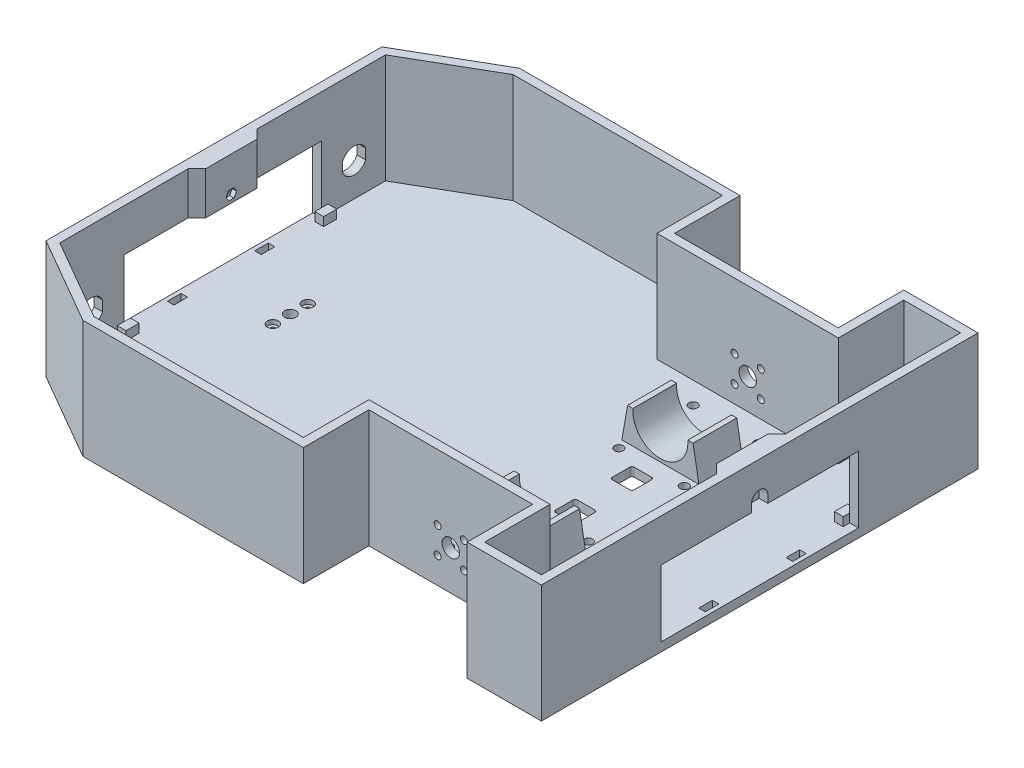
SolidWorks part; units mm, degrees
ref_plane "Front Plane" through (0, 0, 0) normal (0, 0, 1) x (1, 0, 0)
ref_plane "Top Plane" through (0, 0, 0) normal (0, 1, 0) x (1, 0, 0)
ref_plane "Right Plane" through (0, 0, 0) normal (1, 0, 0) x (0, 0, -1)
sketch "Sketch1" plane through (0, 0, 0) normal (0, 1, 0) x (1, 0, 0)
  line L0 (-85, 100) -> (125, 100)
  line L1 (-125, 100) -> (125, 100) construction
  line L2 (-125, 100) -> (-125, -100) construction
  line L3 (-125, -100) -> (125, -100) construction
  line L4 (125, 100) -> (125, -100) construction
  line L6 (125, 100) -> (125, -100)
  line L8 (-125, -76.906) -> (-125, 76.906)
  line L9 (-125, 76.906) -> (-85, 100)
  line L10 (-125, 0) -> (125, 0) construction
  line L12 (-85, -100) -> (125, -100)
  line L13 (-125, -76.906) -> (-85, -100)
  point P4 (0, 100)
  point P6 (-125, 0)
  point P9 (0, 0)
  dimension "D1" = 250
  dimension "D2" = 200
  dimension "D3" = 60
  dimension "D5" = 40
extrude "Boss-Extrude1" add sketch "Sketch1" along normal blind 54
shell "Shell1" thickness 4 removed face at (-28.3333, 54, 0)
sketch "Sketch7" plane through (0, 54, 0) normal (0, 1, 0) x (1, 0, 0)
  line L0 (-85, -100) -> (125, -100) construction
  line L1 (16, -70) -> (91, -70)
  line L2 (16, -70) -> (16, -100)
  line L3 (16, -100) -> (91, -100)
  line L4 (91, -70) -> (91, -100)
  line L5 (121, -96) -> (121, 96) construction
  dimension "D1" = 30
  dimension "D2" = 75
  dimension "D3" = 30
extrude "Cut-Extrude4" cut sketch "Sketch7" against normal up to next
sketch "Sketch8" plane through (0, 4, 0) normal (0, 1, 0) x (1, 0, 0)
  line L0 (16, -96) -> (16, -70)
  line L1 (16, -70) -> (91, -70)
  line L2 (91, -70) -> (91, -96)
  line L3 (12, -96) -> (12, -66)
  line L4 (12, -66) -> (95, -66)
  line L5 (95, -66) -> (95, -96)
  line L6 (16, -96) -> (12, -96)
  line L7 (91, -96) -> (95, -96)
  dimension "D1" = 4
extrude "Boss-Extrude3" add sketch "Sketch8" along normal up to surface (50 mm away) contours L3 L4 L5 L7 L2 L1 L0 L6 up to face at (-7.741, 54, 24.5)
sketch "Sketch9" plane through (0, 0, 70) normal (0, 0, 1) x (1, 0, 0)
  line L1 (91, 54) -> (16, 54) construction
  line L2 (91, 0) -> (16, 0) construction
  point P4 (53.5, 54)
  line B0 (59.5104, 11.9896) -> (47.4896, 24.0104) construction
  circle B1 centre (53.5, 18) radius 4
  circle B2 centre (59.5104, 11.9896) radius 1.6
  circle B3 centre (47.4896, 24.0104) radius 1.6
  circle B4 centre (53.5, 18) radius 12.5 construction
  line B5 (47.4896, 11.9896) -> (59.5104, 24.0104) construction
  circle B6 centre (53.5, 18) radius 4
  circle B7 centre (47.4896, 11.9896) radius 1.6
  circle B8 centre (59.5104, 24.0104) radius 1.6
  circle B9 centre (53.5, 18) radius 12.5 construction
  dimension "D1" = 18
sketch_block_instance "Block-JGA25-371-1"
sketch_block "Block1" parameters "D1"=8, "D3"=3.2, "D4"=25, "D2"=17
sketch_block_instance "Block1-1"
extrude "Cut-Extrude5" cut sketch "Sketch9" against normal up to surface (4 mm away) contours B1 | B7 | B3 | B8 | B2 region at (53.5, 18, 70) region at (59.5104, 11.9896, 70) region at (47.4896, 24.0104, 70) region at (47.4896, 11.9896, 70) region at (59.5104, 24.0104, 70) up to face at (53.5, 29, 66)
sketch "Sketch10" plane through (0, 4, 0) normal (0, 1, 0) x (1, 0, 0)
  line L0 (95, -66) -> (12, -66) construction
  line L1 (38.5, -26) -> (68.5, -26)
  line L2 (38.5, -26) -> (38.5, -46)
  line L3 (38.5, -46) -> (68.5, -46)
  line L4 (68.5, -26) -> (68.5, -46)
  line L5 (91, -70) -> (16, -70) construction
  point P9 (53.5, -70)
  point P10 (53.5, -46)
  dimension "D1" = 30
  dimension "D2" = 20
  dimension "D3" = 20
extrude "Boss-Extrude4" add sketch "Sketch10" along normal blind 15
sketch "Sketch11" plane through (0, 0, 46) normal (0, 0, 1) x (1, 0, 0)
  circle A0 centre (53.5, 18) radius 12.6
  dimension "D1" = 25.2
extrude "Cut-Extrude6" cut sketch "Sketch11" against normal up to surface (20 mm away) up to face at (53.5, 11.5, 26)
sketch "Sketch12" plane through (0, 4, 0) normal (0, 1, 0) x (1, 0, 0)
  line L0 (12, -66) -> (95, -66) construction
  line L1 (48.5, -8) -> (58.5, -8)
  line L2 (48.5, -8) -> (48.5, -18)
  line L3 (48.5, -18) -> (58.5, -18)
  line L4 (58.5, -8) -> (58.5, -18)
  line L5 (91, -70) -> (16, -70) construction
  point P9 (53.5, -70)
  point P10 (53.5, -18)
  dimension "D1" = 10
  dimension "D2" = 48
extrude "Cut-Extrude7" cut sketch "Sketch12" against normal through all
fillet "Fillet1" radius 1 4 edges at (48.5, 2, 18) (58.5, 2, 18) (58.5, 2, 8) (48.5, 2, 8)
chamfer "Chamfer1" distance 15 angle 10 2 edges at (38.5, 4, 36) (68.5, 4, 36) first distance on face at (38.5, 11.5, 36) first distance on face at (68.5, 11.5, 36)
sketch "Sketch36" plane through (0, 4, 0) normal (0, 1, 0) x (1, 0, 0)
  line L0 (91, -70) -> (16, -70) construction
  line L2 (38.5, -22) -> (68.5, -22) construction
  line L3 (38.5, -22) -> (38.5, -56) construction
  line L4 (38.5, -56) -> (68.5, -56) construction
  line L5 (68.5, -22) -> (68.5, -56) construction
  circle A0 centre (68.5, -56) radius 2
  circle A1 centre (38.5, -56) radius 2
  circle A2 centre (38.5, -22) radius 2
  circle A3 centre (68.5, -22) radius 2
  point P6 (53.5, -70)
  point P12 (53.5, -56)
  dimension "D1" = 4
  dimension "D2" = 30
  dimension "D3" = 34
extrude "Cut-Extrude22" cut sketch "Sketch36" against normal up to next
mirror "Mirror2" about plane through (0, 0, 0) normal (0, 0, 1) of "Cut-Extrude22", "Fillet1", "Cut-Extrude7", "Cut-Extrude5", "Boss-Extrude3", "Cut-Extrude4", "Cut-Extrude6", "Boss-Extrude4", "Chamfer1"
sketch "Sketch13" plane through (0, 4, 0) normal (0, 1, 0) x (1, 0, 0)
  line L0 (-90, 0) -> (90, 0) construction
  circle A0 centre (-90, 0) radius 2.6
  circle A1 centre (90, 0) radius 2.6
  point P2 (0, 0)
  circle B0 centre (-90.0005, -8) radius 1.1
  circle B1 centre (-89.9995, 8) radius 1.1
  circle B2 centre (89.9995, -8) radius 1.1
  circle B3 centre (90.0005, 8) radius 1.1
  dimension "D2" = 5.2
  dimension "D1" = 180
sketch_block_instance "Ball-Caster-1"
sketch_block "Ball-Caster" parameters "D1"=16, "D2"=2.2, "D3"=16
sketch_block_instance "Ball-Caster-2"
extrude "Cut-Extrude8" cut sketch "Sketch13" against normal blind 10
sketch "Sketch14" plane through (0, 4, 0) normal (0, 1, 0) x (1, 0, 0)
  circle A0 centre (-89.9995, 8) radius 2.5
  circle A1 centre (-90.0005, -8) radius 2.5
  circle A2 centre (90.0005, 8) radius 2.5
  circle A3 centre (89.9995, -8) radius 2.5
  dimension "D1" = 5
extrude "Cut-Extrude9" cut sketch "Sketch14" against normal blind 2
sketch "Sketch16" plane through (-125, 0, 0) normal (-1, 0, 0) x (0, 0, 1)
  line L1 (-45.25, 34.5) -> (45.25, 34.5)
  line L2 (-45.25, 34.5) -> (-45.25, 4)
  line L3 (-45.25, 4) -> (45.25, 4)
  line L4 (45.25, 34.5) -> (45.25, 4)
  line L5 (-76.906, 0) -> (76.906, 0) construction
  point P6 (0, 34.5)
  dimension "D1" = 30.5
  dimension "D2" = 90.5
  dimension "D5" = 4
extrude "Cut-Extrude10" cut sketch "Sketch16" against normal blind 4.2 contours L4 L1 L2 L3 region at (-125, 19.25, 0)
sketch "Sketch19" plane through (0, 4, 0) normal (0, 1, 0) x (1, 0, 0)
  line L0 (-125, 0) -> (0, 0) construction
  line L1 (-123.2, 23.1) -> (-120.2, 23.1)
  line L2 (-123.2, 23.1) -> (-123.2, 16.9)
  line L3 (-123.2, 16.9) -> (-120.2, 16.9)
  line L4 (-120.2, 23.1) -> (-120.2, 16.9)
  line L11 (-125, 45.25) -> (-125, -45.25) construction
  line L12 (-123.2, -16.9) -> (-120.2, -16.9)
  line L13 (-120.2, -23.1) -> (-120.2, -16.9)
  line L14 (-123.2, -23.1) -> (-120.2, -23.1)
  line L15 (-123.2, -23.1) -> (-123.2, -16.9)
  point P6 (-120.2, 20)
  dimension "D1" = 3
  dimension "D2" = 6.2
  dimension "D3" = 1.8
  dimension "D4" = 20
extrude "Cut-Extrude12" cut sketch "Sketch19" against normal up to next
sketch "Sketch26" plane through (-125, 0, 0) normal (-1, 0, 0) x (0, 0, 1)
  line L2 (-45.25, 4) -> (45.25, 4) construction
  line L3 (-76.906, 0) -> (76.906, 0) construction
  line L4 (-45.25, 34.5) -> (45.25, 34.5) construction
  line L5 (-3.75, 38) -> (3.75, 38)
  line L6 (-3.75, 38) -> (-3.75, 34.5)
  line L7 (-3.75, 34.5) -> (3.75, 34.5)
  line L8 (3.75, 38) -> (3.75, 34.5)
  circle A0 centre (0, 38) radius 3.75
  point P5 (0, 0)
  dimension "D1" = 7.5
  dimension "D2" = 34
extrude "Cut-Extrude17" cut sketch "Sketch26" against normal up to next contours L5 A0 | L5 A0 L7 | L6 L5 L8 L7 region at (-125, 39.5915, 0) region at (-125, 36.4504, 0)
sketch "Sketch27" plane through (-121, 0, 0) normal (1, 0, 0) x (0, 0, -1)
  line L0 (74.5966, 54) -> (-74.5966, 54) construction
  line L1 (-9.75, 54) -> (9.75, 54)
  line L2 (-9.75, 54) -> (-9.75, 34.5)
  line L3 (-9.75, 34.5) -> (9.75, 34.5)
  line L4 (9.75, 54) -> (9.75, 34.5)
  line L5 (3.75, 34.5) -> (45.25, 34.5) construction
  point P8 (0, 54)
  point P9 (0, 54)
extrude "Boss-Extrude6" add sketch "Sketch27" along normal blind 4
sketch "Sketch28" plane through (-117, 0, 0) normal (1, 0, 0) x (0, 0, -1)
  line L0 (9.75, 54) -> (-9.75, 54) construction
  line L1 (1.2124, 35.9) -> (2.4249, 38)
  line L2 (2.4249, 38) -> (1.2124, 40.1)
  line L3 (1.2124, 40.1) -> (-1.2124, 40.1)
  line L4 (-1.2124, 40.1) -> (-2.4249, 38)
  line L5 (-2.4249, 38) -> (-1.2124, 35.9)
  line L6 (-1.2124, 35.9) -> (1.2124, 35.9)
  circle A0 centre (0, 38) radius 2.1 construction
  point P11 (0, 54)
  dimension "D1" = 4.2
  dimension "D2" = 34
extrude "Cut-Extrude18" cut sketch "Sketch28" against normal blind 2
sketch "Sketch29" plane through (-121, 0, 0) normal (-1, 0, 0) x (0, 0, 1)
  circle A0 centre (0, 38) radius 1.1
  dimension "D1" = 2.2
extrude "Cut-Extrude19" cut sketch "Sketch29" against normal up to next
sketch "Sketch30" plane through (0, 4, 0) normal (0, 1, 0) x (1, 0, 0)
  line L0 (-125, 0) -> (0, 0) construction
  line L1 (-125, 45.25) -> (-125, -45.25) construction
  line L2 (-121, 74.5966) -> (-121, 45.25) construction
  line L3 (-121, 48.25) -> (-117, 48.25)
  line L4 (-121, 48.25) -> (-121, 42.25)
  line L5 (-121, 42.25) -> (-117, 42.25)
  line L6 (-117, 48.25) -> (-117, 42.25)
  line L7 (-121, -42.25) -> (-117, -42.25)
  line L8 (-117, -48.25) -> (-117, -42.25)
  line L9 (-121, -48.25) -> (-117, -48.25)
  line L10 (-121, -48.25) -> (-121, -42.25)
  point P11 (-121, 45.25)
  dimension "D1" = 4
  dimension "D2" = 6
extrude "Boss-Extrude7" add sketch "Sketch30" along normal blind 4
mirror "Mirror4" about plane through (0, 0, 0) normal (1, 0, 0) of "Cut-Extrude12", "Cut-Extrude10", "Cut-Extrude17", "Cut-Extrude19", "Cut-Extrude18", "Boss-Extrude6", "Boss-Extrude7"
chamfer "Chamfer3" distance 6 angle 45 4 edges at (-121, 44.25, 9.75) (-121, 44.25, -9.75) (121, 44.25, 9.75) (121, 44.25, -9.75)
sketch "Sketch33" plane through (0, 4, 0) normal (0, 1, 0) x (1, 0, 0)
  line L0 (53.5, 66) -> (53.5, -66) construction
  line L1 (-108, 35) -> (-28, 35) construction
  line L2 (-108, 35) -> (-108, -35) construction
  line L3 (-108, -35) -> (-28, -35) construction
  line L4 (-28, 35) -> (-28, -35) construction
  line L5 (-111, 38) -> (-25, 38) construction
  line L6 (-25, 38) -> (-25, -38) construction
  line L7 (-111, -38) -> (-25, -38) construction
  line L8 (-111, 38) -> (-111, -38) construction
  line L9 (-121, 74.5966) -> (-121, 15.75) construction
  line L10 (-28, -12.5) -> (-25, -12.5)
  line L11 (-28, -12.5) -> (-28, 12.5)
  line L12 (-28, 12.5) -> (-25, 12.5)
  line L13 (-25, -12.5) -> (-25, 12.5)
  line L14 (-55.5, 38) -> (-80.5, 38)
  line L15 (-55.5, 38) -> (-55.5, 35)
  line L16 (-55.5, 35) -> (-80.5, 35)
  line L17 (-80.5, 38) -> (-80.5, 35)
  line L18 (-80.5, -35) -> (-55.5, -35)
  line L19 (-80.5, -35) -> (-80.5, -38)
  line L20 (-80.5, -38) -> (-55.5, -38)
  line L21 (-55.5, -35) -> (-55.5, -38)
  line L26 (12, 66) -> (95, 66) construction
  line L27 (12, -66) -> (95, -66) construction
  line L28 (187.5, -38) -> (162.5, -38)
  line L29 (162.5, -35) -> (162.5, -38)
  line L30 (187.5, -35) -> (162.5, -35)
  line L31 (187.5, -35) -> (187.5, -38)
  line L32 (135, 12.5) -> (132, 12.5)
  line L33 (132, -12.5) -> (132, 12.5)
  line L34 (135, -12.5) -> (132, -12.5)
  line L35 (135, -12.5) -> (135, 12.5)
  line L36 (162.5, 35) -> (187.5, 35)
  line L37 (187.5, 38) -> (187.5, 35)
  line L38 (162.5, 38) -> (187.5, 38)
  line L39 (162.5, 38) -> (162.5, 35)
  point P4 (-28, 0)
  point P16 (-28, 0)
  point P21 (-68, 35)
  point P22 (-68, 35)
  point P27 (-68, -35)
  point P28 (-68, -35)
  dimension "D1" = 80
  dimension "D2" = 70
  dimension "D3" = 3
  dimension "D4" = 10
  dimension "D5" = 25
extrude "Boss-Extrude9" [suppressed] add sketch "Sketch33" along normal blind 15
chamfer "Chamfer8" [suppressed] distance 15 angle 10
sketch "Sketch31" plane through (0, 54, 0) normal (0, 1, 0) x (1, 0, 0)
  line L0 (16, 100) -> (-85, 100) construction
  line L1 (-55, 100) -> (55, 100)
  line L2 (-55, 100) -> (-55, -100)
  line L3 (-55, -100) -> (55, -100)
  line L4 (55, 100) -> (55, -100)
  line L5 (91, -100) -> (125, -100) construction
  point P8 (0, -100)
  dimension "D1" = 110
extrude "Cut-Extrude20" [suppressed] cut sketch "Sketch31" against normal blind 8
chamfer "Chamfer6" [suppressed] distance 8 angle 45
sketch "Sketch34" plane through (-125, 0, 0) normal (-1, 0, 0) x (0, 0, 1)
  line L0 (55, 21.5952) -> (55, 16.9048)
  line L1 (65.5, 21.5952) -> (65.5, 16.9048)
  line L2 (45.25, 34.5) -> (45.25, 4) construction
  line L3 (-45.25, 34.5) -> (-45.25, 4) construction
  line L4 (0, 54) -> (0, 0) construction
  line L5 (-76.906, 54) -> (76.906, 54) construction
  line L6 (-76.906, 0) -> (76.906, 0) construction
  line L7 (-65.5, 21.5952) -> (-65.5, 16.9048)
  line L8 (-55, 21.5952) -> (-55, 16.9048)
  circle A0 centre (60.25, 19.25) radius 5.75
  circle A1 centre (-60.25, 19.25) radius 5.75
  point P6 (-45.25, 19.25)
  point P7 (45.25, 19.25)
  dimension "D1" = 11.5
  dimension "D2" = 10.5
  dimension "D3" = 15
extrude "Cut-Extrude21" cut sketch "Sketch34" against normal up to next contours A1 L8 L7 | L1 A0 L0 region at (-125, 19.25, 60.25) region at (-125, 19.25, -60.25)
